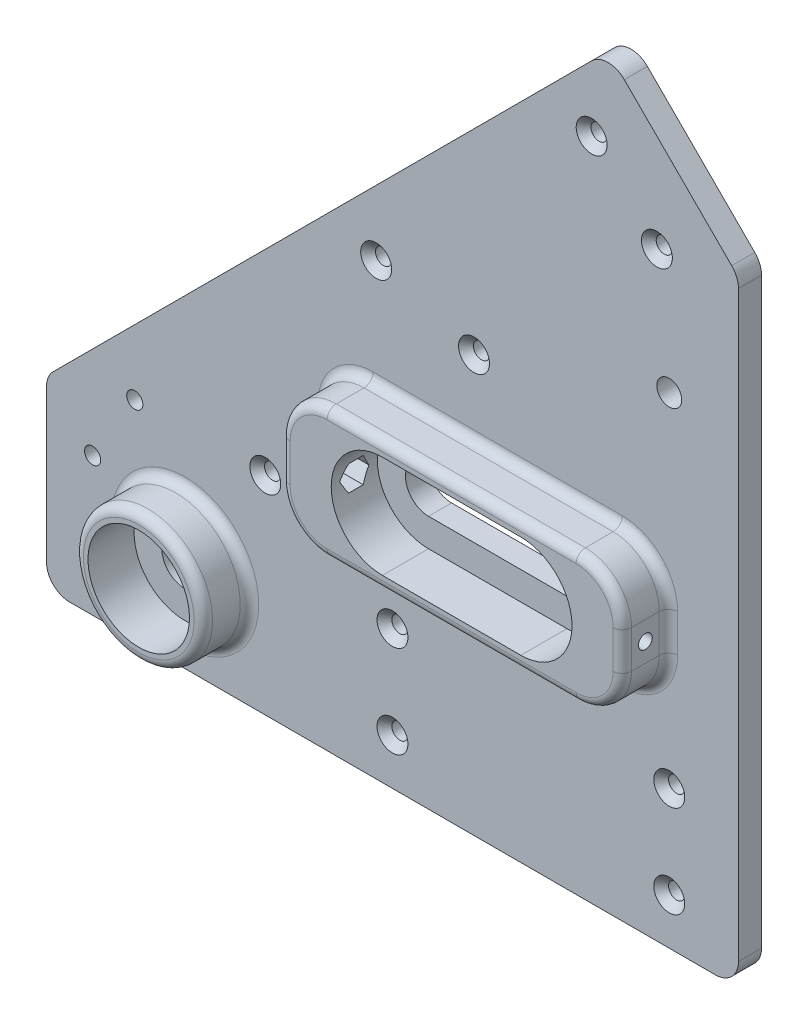
SolidWorks part; units mm, degrees
ref_plane "Front Plane" through (0, 0, 0) normal (0, 0, 1) x (1, 0, 0)
ref_plane "Top Plane" through (0, 0, 0) normal (0, 1, 0) x (1, 0, 0)
ref_plane "Right Plane" through (0, 0, 0) normal (1, 0, 0) x (0, 0, -1)
sketch "Sketch1" plane through (0, 0, 0) normal (0, 0, 1) x (1, 0, 0)
  line L0 (-75, 20) -> (46.7157, 141.7157)
  line L1 (-18.4315, 20) -> (75, 20) construction
  line L2 (-75, 20) -> (-75, -20)
  line L3 (-75, -20) -> (75, -20)
  line L4 (75, 20) -> (75, -20)
  line L5 (-75, 20) -> (75, -20) construction
  line L6 (-75, -20) -> (75, 20) construction
  line L7 (-75, -20) -> (75, -20)
  line L11 (46.7157, 141.7157) -> (75, 113.4315)
  line L12 (75, 113.4315) -> (-18.4315, 20) construction
  line L13 (-75, 0) -> (75, 0) construction
  line L14 (-75, 10) -> (75, 10) construction
  line L15 (-75, -10) -> (75, -10) construction
  line L16 (60.8579, 127.5736) -> (-46.7157, 20) construction
  line L17 (-75, 20) -> (-18.4315, 20) construction
  line L18 (53.7868, 134.6447) -> (-60.8579, 20) construction
  line L19 (67.9289, 120.5025) -> (-32.5736, 20) construction
  line L20 (75, 113.4315) -> (75, 20)
  line L21 (43.1802, 124.0381) -> (57.3223, 109.8959) construction
  line L22 (60, -10) -> (60, 10) construction
  line L23 (-65, -10) -> (-65, 10) construction
  line L24 (7.8199, 40) -> (37.8199, 40) construction
  line L25 (7.8199, 45) -> (37.8199, 45)
  line L26 (7.8199, 35) -> (37.8199, 35)
  line L27 (60, 10) -> (60, 98.4315) construction
  circle A0 centre (-45, 0) radius 5
  circle A1 centre (22.8199, 40) radius 5 construction
  circle A2 centre (-65, -10) radius 1.75
  circle A3 centre (0, 10) radius 1.75
  circle A4 centre (60, -10) radius 1.75
  circle A5 centre (-55.8579, 25) radius 1.75
  circle A6 centre (43.1802, 124.0381) radius 1.75
  circle A8 centre (-27.5736, 25) radius 1.75
  circle A9 centre (57.3223, 109.8959) radius 1.75
  circle A10 centre (22.8199, 40) radius 4 construction
  circle A11 centre (-3.5355, 77.3223) radius 1.75
  circle A12 centre (17.6777, 70.2513) radius 1.75
  circle A13 centre (60, 10) radius 1.75
  circle A14 centre (-65, 10) radius 1.75
  circle A15 centre (0, -10) radius 1.75
  arc A16 (7.8199, 45) -> (7.8199, 35) centre (7.8199, 40) ccw
  arc A17 (37.8199, 35) -> (37.8199, 45) centre (37.8199, 40) ccw
  circle A18 centre (60, 84.2893) radius 2.7
  point P0 (0, 0)
  point P50 (22.8199, 40)
  dimension "D8" = 10
  dimension "D11" = 10
  dimension "D12" = 3.5
  dimension "D17" = 30
  dimension "D18" = 5.4
  dimension "D1" = 40
  dimension "D2" = 40
  dimension "D3" = 45
  dimension "D4" = 10
  dimension "D5" = 10
  dimension "D6" = 10
  dimension "D7" = 10
  dimension "D9" = 30
  dimension "D10" = 150
  dimension "D13" = 10
  dimension "D14" = 15
  dimension "D15" = 5
  dimension "D16" = 15
  dimension "D19" = 10
extrude "Boss-Extrude1" add sketch "Sketch1" along normal blind 5 contours L20 L11 L0 L2 L3 L4 A0 region at (-12.5825, 79.2982, 0)
sketch "Sketch2" plane through (0, 0, 5) normal (0, 0, 1) x (1, 0, 0)
  line L3 (7.8199, 40) -> (37.8199, 40) construction
  line L4 (7.8199, 51.1) -> (37.8199, 51.1)
  line L5 (7.8199, 28.9) -> (37.8199, 28.9)
  line L6 (-14.1801, 54.1) -> (59.8199, 54.1)
  line L7 (-14.1801, 54.1) -> (-14.1801, 25.9)
  line L8 (-14.1801, 25.9) -> (59.8199, 25.9)
  line L9 (59.8199, 54.1) -> (59.8199, 25.9)
  line L10 (-14.1801, 54.1) -> (59.8199, 25.9) construction
  line L11 (-14.1801, 25.9) -> (59.8199, 54.1) construction
  circle A0 centre (-45, 0) radius 11
  circle A1 centre (-45, 0) radius 14
  circle A2 centre (22.8199, 40) radius 11.1 construction
  circle A3 centre (22.8199, 40) radius 14 construction
  arc A6 (7.8199, 51.1) -> (7.8199, 28.9) centre (7.8199, 40) ccw
  arc A7 (37.8199, 28.9) -> (37.8199, 51.1) centre (37.8199, 40) ccw
  point P19 (22.8199, 40)
  dimension "D1" = 22
  dimension "D2" = 28
  dimension "D3" = 22.2
  dimension "D4" = 28
  dimension "D5" = 3
  dimension "D6" = 22
extrude "Boss-Extrude2" add sketch "Sketch2" along normal blind 10
chamfer "Chamfer1" distance 1.6 angle 45 9 edges at (-25.8236, 25, 5) (61.75, -10, 5) (61.75, 10, 5) (1.75, -10, 5) (1.75, 10, 5) (19.4277, 70.2513, 5) (-1.7855, 77.3223, 5) (59.0723, 109.8959, 5) (44.9302, 124.0381, 5)
fillet "Fillet1" radius 10 4 edges at (59.8199, 25.9, 10) (59.8199, 54.1, 10) (-14.1801, 25.9, 10) (-14.1801, 54.1, 10)
sketch "Sketch3" plane through (-14.1801, 0, 0) normal (-1, 0, 0) x (0, 0, 1)
  line L0 (10, 44.1) -> (10, 35.9) construction
  line L1 (15, 44.1) -> (5, 44.1) construction
  line L2 (5, 35.9) -> (15, 35.9) construction
  circle A0 centre (10, 40) radius 1.5
  point P8 (8.5, 39.5433)
  dimension "D1" = 3
extrude "Cut-Extrude1" cut sketch "Sketch3" against normal through all
ref_plane "Plane1" through (-3.2801, 0, 0) normal (1, 0, 0) x (0, 0, -1)
sketch "Sketch4" plane through (-3.2801, 0, 0) normal (1, 0, 0) x (0, 0, -1)
  line L1 (-6.8246, 40) -> (-8.4123, 42.75)
  line L2 (-8.4123, 42.75) -> (-11.5877, 42.75)
  line L3 (-11.5877, 42.75) -> (-13.1754, 40)
  line L4 (-13.1754, 40) -> (-11.5877, 37.25)
  line L5 (-11.5877, 37.25) -> (-8.4123, 37.25)
  line L6 (-8.4123, 37.25) -> (-6.8246, 40)
  circle A0 centre (-10, 40) radius 2.75 construction
  dimension "D1" = 5.5
extrude "Cut-Extrude3" cut sketch "Sketch4" against normal blind 5 and the other way offset from surface 6 other way up to face at (59.8199, 40, 11.5)
fillet "Fillet2" radius 2 9 edges at (56.891, 51.1711, 5) (59.8199, 40, 5) (56.891, 28.8289, 5) (22.8199, 25.9, 5) (-11.2511, 28.8289, 5) (-14.1801, 40, 5) (-11.2511, 51.1711, 5) (-31, 0, 5) (22.8199, 54.1, 5)
fillet "Fillet3" radius 2 9 edges at (56.891, 51.1711, 15) (59.8199, 40, 15) (56.891, 28.8289, 15) (22.8199, 25.9, 15) (-11.2511, 28.8289, 15) (-14.1801, 40, 15) (-11.2511, 51.1711, 15) (-31, 0, 15) (22.8199, 54.1, 15)
fillet "Fillet4" radius 5 5 edges at (75, 113.4315, 2.5) (46.7157, 141.7157, 2.5) (75, -20, 2.5) (-75, -20, 2.5) (-75, 20, 2.5)
